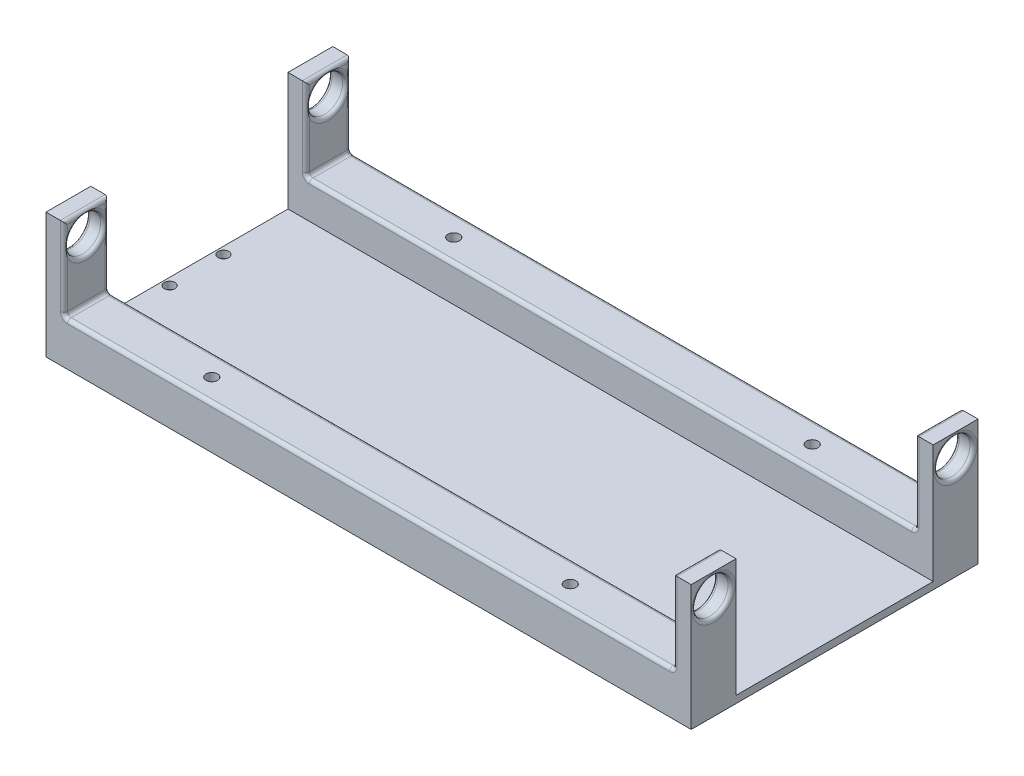
SolidWorks part; units mm, degrees
ref_plane "Front Plane" through (0, 0, 0) normal (0, 0, 1) x (1, 0, 0)
ref_plane "Top Plane" through (0, 0, 0) normal (0, 1, 0) x (1, 0, 0)
ref_plane "Right Plane" through (0, 0, 0) normal (1, 0, 0) x (0, 0, -1)
sketch "Sketch1" plane through (0, 0, 0) normal (0, 1, 0) x (1, 0, 0)
  line L1 (-90, -40) -> (90, -40)
  line L2 (-90, -40) -> (-90, 40)
  line L3 (-90, 40) -> (90, 40)
  line L4 (90, -40) -> (90, 40)
  line L5 (-90, -40) -> (90, 40) construction
  line L6 (-90, 40) -> (90, -40) construction
  point P0 (0, 0)
  dimension "D1" = 180
  dimension "D2" = 80
extrude "Boss-Extrude1" add sketch "Sketch1" along normal blind 2
sketch "Sketch2" plane through (0, 2, 0) normal (0, 1, 0) x (1, 0, 0)
  line L0 (90, -40) -> (90, 40) construction
  line L1 (-90, -40) -> (90, -40)
  line L2 (-90, -40) -> (-90, -27.5)
  line L3 (-90, -27.5) -> (90, -27.5)
  line L4 (90, -40) -> (90, -27.5)
  line L6 (-90, 40) -> (90, 40)
  line L7 (-90, 40) -> (-90, 27.5)
  line L8 (-90, 27.5) -> (90, 27.5)
  line L9 (90, 40) -> (90, 27.5)
  dimension "D1" = 55
extrude "Boss-Extrude2" add sketch "Sketch2" along normal blind 10
sketch "Sketch3" plane through (0, 0, -40) normal (0, 0, -1) x (-1, 0, 0)
  line L4 (-108.5, 29) -> (90, 29) construction
  line L5 (90, 12) -> (90, 0) construction
  line L7 (-90, 12) -> (-85, 12)
  line L8 (-90, 12) -> (-90, 35)
  line L9 (-90, 35) -> (-85, 35)
  line L10 (-85, 12) -> (-85, 35)
  dimension "D2" = 23
  dimension "D1" = 5
extrude "Boss-Extrude3" add sketch "Sketch3" against normal blind 12.5
sketch "Sketch8" plane through (85, 0, 0) normal (-1, 0, 0) x (0, 0, 1)
  line L0 (-27.5, 35) -> (-40, 35) construction
  circle A0 centre (-33.75, 28.75) radius 5
  point P5 (-33.75, 35)
  dimension "D1" = 10
  dimension "D2" = 6.25
extrude "Cut-Extrude1" cut sketch "Sketch8" against normal through all contours A0
mirror "Mirror2" about plane through (0, 0, 0) normal (0, 0, 1) of "Cut-Extrude1", "Boss-Extrude3"
mirror "Mirror3" about plane through (0, 0, 0) normal (1, 0, 0) of "Cut-Extrude1", "Mirror2", "Boss-Extrude3"
fillet "Fillet1" radius 1 28 edges at (85, 23.5, 27.5) (85, 23.5, 40) (-85, 23.5, 40) (-85, 23.5, 27.5) (85, 23.5, -27.5) (85, 23.5, -40) (-85, 23.5, -27.5) (-85, 23.5, -40) (85, 12, 33.75) (0, 12, 40) (-85, 12, 33.75) (0, 12, 27.5) (85, 12, -33.75) (0, 12, -27.5) (-85, 12, -33.75) (0, 12, -40) (-85, 28.75, 28.75) (-90, 28.75, 28.75) (-85, 28.75, -28.75) (-90, 28.75, -28.75) (85, 28.75, 28.75) (90, 28.75, 28.75) (85, 28.75, -28.75) (90, 28.75, -28.75) (85, 35, 33.75) (85, 35, -33.75) (-85, 35, 33.75) (-85, 35, -33.75)
sketch "Sketch9" plane through (0, 12, 0) normal (0, 1, 0) x (1, 0, 0)
  line L0 (84, -39) -> (84, -28.5) construction
  line L1 (84, 28.5) -> (84, 39) construction
  line L2 (-90, -27.5) -> (-90, -40) construction
  line L3 (90, -27.5) -> (90, -40) construction
  circle A0 centre (50, -33.75) radius 1.6
  circle A1 centre (-50, -33.75) radius 1.6
  circle A2 centre (50, 33.75) radius 1.6
  circle A3 centre (-50, 33.75) radius 1.6
  point P14 (84, -33.75)
  point P17 (84, 33.75)
  dimension "D1" = 3.2
  dimension "D2" = 40
  dimension "D3" = 40
extrude "Cut-Extrude2" cut sketch "Sketch9" against normal through all
sketch "Sketch10" plane through (0, 2, 0) normal (0, 1, 0) x (1, 0, 0)
  line L0 (-90, 0) -> (-86, 0) construction
  line L1 (-90, 27.5) -> (-90, -27.5) construction
  line L2 (-88, 7.5) -> (-88, -7.5) construction
  circle A0 centre (-88, 7.5) radius 1.5
  circle A1 centre (-88, -7.5) radius 1.5
  point P9 (-88, 0)
  point P11 (0, 0)
  point P12 (0, 0)
  dimension "D1" = 3
  dimension "D2" = 2
  dimension "D3" = 15
extrude "Cut-Extrude3" cut sketch "Sketch10" against normal up to surface (2 mm away) up to face at (-50, 0, 35.35)
